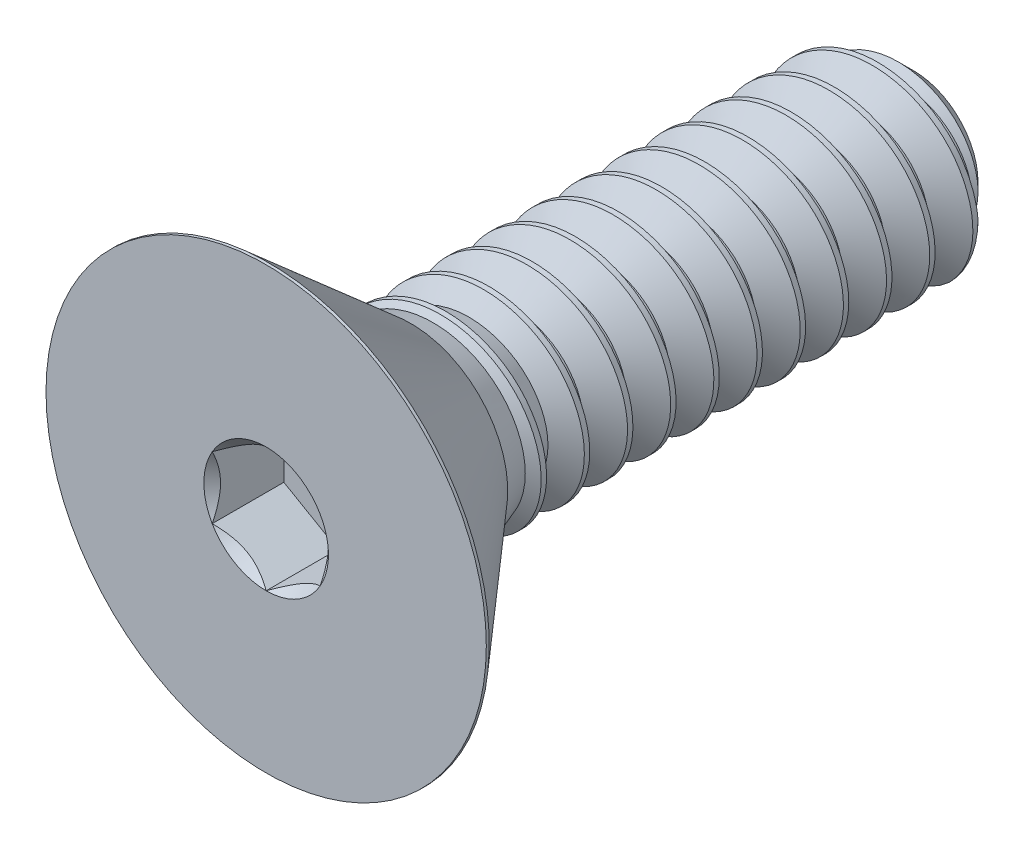
SolidWorks part; units mm, degrees
ref_plane "Front Plane" through (0, 0, 0) normal (0, 0, 1) x (1, 0, 0)
ref_plane "Top Plane" through (0, 0, 0) normal (0, 1, 0) x (1, 0, 0)
ref_plane "Right Plane" through (0, 0, 0) normal (1, 0, 0) x (0, 0, -1)
sketch "Sketch1" plane through (0, 0, 0) normal (1, 0, 0) x (0, 0, -1)
  line L0 (-4.7625, 0) -> (4.7625, 0) construction
  line L1 (-4.7625, 0) -> (-4.7625, 3.2385)
  line L2 (-4.7625, 3.2385) -> (-4.7203, 3.2385)
  line L3 (-4.7203, 3.2385) -> (-2.6543, 1.4425)
  line L4 (-4.7203, -3.2385) -> (-2.6543, -1.4425)
  line L5 (4.7625, 0) -> (4.7625, 1.4224)
  line L6 (4.7625, 1.4224) -> (-2.6543, 1.4224)
  line L7 (4.2862, 1.4224) -> (4.7625, 0.9461)
  line L8 (4.7228, 1.4911) -> (5.0403, 0.9412) construction
  line L9 (5.0403, 0.9412) -> (5.3578, 1.4911) construction
  line L10 (5.3578, 1.4911) -> (4.7228, 1.4911) construction
  line L11 (4.7427, 1.4568) -> (5.338, 1.4568)
  line L12 (5.338, 1.4568) -> (5.08, 1.01)
  line L13 (5.08, 1.01) -> (5.0006, 1.01)
  line L14 (5.0006, 1.01) -> (4.7427, 1.4568)
  line L15 (5.0403, 1.01) -> (5.0403, 0.9412) construction
  line L16 (4.7625, 1.4224) -> (5.3181, 1.4224) construction
  line L17 (5.0403, 1.4911) -> (5.0403, 1.4224) construction
  line L18 (4.7625, -1.4224) -> (-2.6543, -1.4224)
  arc A0 (-2.6543, 1.4425) -> (-2.6005, 1.4224) centre (-2.6005, 1.5044) ccw
  point P2 (0, 0)
  point P23 (-3.7084, 0)
  point P27 (5.0403, 1.4568)
  point P30 (3.81, -1.4224)
  point P31 (-2.6543, 3.2385)
  point P34 (-4.7203, -3.2385)
  dimension "Length" = 9.525
  dimension "Head Height" = 2.1082
  dimension "Head Diameter" = 6.477
  dimension "Countersink Angle" = 82
  dimension "Screw Size Decimal Equivalent" = 2.8448
  dimension "Pitch" = 0.635
  dimension "D4" = 0.0794
  dimension "D3" = 45
  dimension "D5" = 0.4763
  dimension "D6" = 1.0541
  dimension "D1" = 0.9525
  dimension "D7" = 0.0422
sketch "Sketch8" plane through (0, 0, 0) normal (0, 0, 1) x (1, 0, 0)
  line L1 (0, 0.9165) -> (-0.7937, 0.4583)
  line L2 (-0.7937, 0.4583) -> (-0.7937, -0.4583)
  line L3 (-0.7937, -0.4583) -> (0, -0.9165)
  line L4 (0, -0.9165) -> (0.7937, -0.4583)
  line L5 (0.7937, -0.4583) -> (0.7937, 0.4583)
  line L6 (0.7937, 0.4583) -> (0, 0.9165)
  circle A0 centre (0, 0) radius 0.7937 construction
  dimension "Drive Size" = 1.5875
sketch "Sketch2" plane through (0, 0, 0) normal (1, 0, 0) x (0, 0, -1)
  line L0 (-4.7203, 3.2385) -> (-2.6543, 1.4425) construction
  line L1 (-4.7625, 0) -> (-4.7625, 3.2385) construction
  line L2 (-4.7203, 3.2385) -> (-2.6312, 1.4224)
  line L3 (-4.7625, 0) -> (-4.7625, 3.2385)
  line L4 (-4.7625, 3.2385) -> (-4.7203, 3.2385) construction
  line L5 (-4.7625, 3.2385) -> (-4.7203, 3.2385)
  line L6 (-2.6312, 1.4224) -> (4.2862, 1.4224)
  line L7 (4.2862, 1.4224) -> (4.7625, 0.9461)
  line L8 (4.7625, 0.9461) -> (4.7625, 0)
  line L9 (4.7625, 0) -> (-4.7625, 0)
revolve "Revolve1" add sketch "Sketch2" angle 360 about L9
sketch "Sketch9" plane through (0, 0, 4.7625) normal (0, 0, 1) x (1, 0, 0)
  line L0 (0.7937, -0.4583) -> (0.7937, 0.4583) construction
  line L1 (0, -0.9165) -> (0.7937, -0.4583) construction
  line L2 (-0.7937, -0.4583) -> (0, -0.9165) construction
  line L3 (-0.7937, 0.4583) -> (-0.7937, -0.4583) construction
  line L4 (0, 0.9165) -> (-0.7937, 0.4583) construction
  line L5 (0.7937, 0.4583) -> (0, 0.9165) construction
  line L6 (0.7937, -0.4583) -> (0.7937, 0.4583)
  line L7 (0, -0.9165) -> (0.7937, -0.4583)
  line L8 (-0.7937, -0.4583) -> (0, -0.9165)
  line L9 (-0.7937, 0.4583) -> (-0.7937, -0.4583)
  line L10 (0, 0.9165) -> (-0.7937, 0.4583)
  line L11 (0.7937, 0.4583) -> (0, 0.9165)
sketch "Sketch10" plane through (0, 0, 4.7625) normal (0, 0, 1) x (1, 0, 0)
  circle A0 centre (0, 0) radius 0.9165
extrude "Cut-Extrude2" cut sketch "Sketch10" against normal up to vertex (1.0541 mm away) draft 45 up to point (0, 0, 3.7084)
extrude "Cut-Extrude1" cut sketch "Sketch9" against normal up to vertex (1.0541 mm away) up to point (0, 0, 3.7084)
ref_plane "Plane1" through (0, 0, 2.6312) normal (0, 0, 1) x (1, 0, 0)
split "Split1" trim tools "Plane1" bodies to split 111 resulting bodies 105 106
sketch "Sketch3" plane through (0, 0, -4.7625) normal (0, 0, -1) x (-1, 0, 0)
  circle A0 centre (0, 0) radius 1.4224 construction
  circle A1 centre (0, 0) radius 1.4224
curve "Helix/Spiral1" pitch 0.635 height 9.525 turns 15
sketch "Sketch4" plane through (0, 0, 0) normal (1, 0, 0) x (0, 0, -1)
  line L0 (4.7427, 1.4568) -> (5.338, 1.4568) construction
  line L1 (5.0006, 1.01) -> (4.7427, 1.4568) construction
  line L2 (5.08, 1.01) -> (5.0006, 1.01) construction
  line L3 (5.338, 1.4568) -> (5.08, 1.01) construction
  line L4 (4.7427, 1.4568) -> (5.338, 1.4568)
  line L5 (5.0006, 1.01) -> (4.7427, 1.4568)
  line L6 (5.08, 1.01) -> (5.0006, 1.01)
  line L7 (5.338, 1.4568) -> (5.08, 1.01)
sweep "Cut-Sweep1" cut profiles "Sketch4" path "Helix/Spiral1" align with end faces yes
sketch "Sketch7" plane through (0, 0, 2.6312) normal (0, 0, 1) x (1, 0, 0)
  circle A0 centre (0, 0) radius 1.4224
extrude "Boss-Extrude2" add sketch "Sketch7" against normal up to next (7.3937 mm away) draft 20
equation "\"D4@Sketch1\" = \"Pitch@Sketch1\" / 8"
equation "\"D5@Sketch1\"=\"Pitch@Sketch1\"*0.75"
equation "\"D4@Helix/Spiral1\"=\"Pitch@Sketch1\""
equation "\"D3@Helix/Spiral1\"=\"Length@Sketch1\""
equation "\"D6@Sketch1\"=\"Head Height@Sketch1\"/2"
equation "\"D1@Sketch1\"=\"Pitch@Sketch1\"*1.5"
equation "\"D7@Sketch1\"=\"Head Height@Sketch1\"*0.02"
